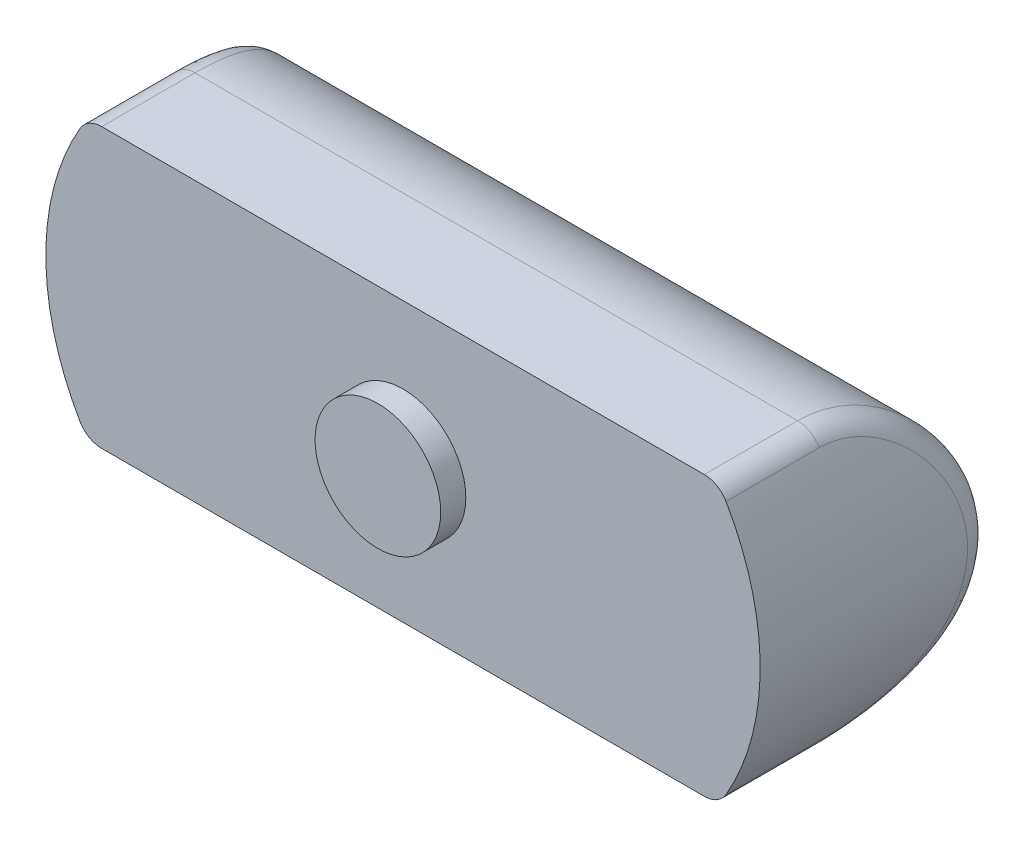
SolidWorks part; units mm, degrees
ref_plane "Front Plane" through (0, 0, 0) normal (0, 0, 1) x (1, 0, 0)
ref_plane "Top Plane" through (0, 0, 0) normal (0, 1, 0) x (1, 0, 0)
ref_plane "Right Plane" through (0, 0, 0) normal (1, 0, 0) x (0, 0, -1)
sketch "Sketch2" plane through (0, 0, 0) normal (0, 0, 1) x (1, 0, 0)
  line L0 (-37.65, 16.64) -> (37.65, 16.64)
  line L1 (42.65, 16.64) -> (42.65, -16.64) construction
  line L2 (37.65, -16.64) -> (-37.65, -16.64)
  line L3 (-42.65, -16.64) -> (-42.65, 16.64) construction
  line L4 (0, 16.64) -> (0, -16.64) construction
  arc A0 (-37.65, 16.64) -> (-37.65, -16.64) centre (-12.461, 0) ccw
  arc A1 (37.65, 16.64) -> (37.65, -16.64) centre (12.461, 0) cw
  point P2 (-34.4657, -12.2734)
  point P5 (42.65, 0)
  point P15 (0, 0)
  point P16 (0, 0)
  point P17 (-33.6669, -16.64)
  dimension "D1" = 33.28
  dimension "D2" = 85.3
  dimension "D3" = 5
  dimension "D4" = 33.28
extrude "Boss-Extrude1" add sketch "Sketch2" along normal blind 27.77
fillet "Fillet1" 2 edges at (0, 16.64, 0) (0, -16.64, 0) type full round first side face at (0, 16.64, 13.885) second side face at (0, -16.64, 13.885) middle face at (0, 0, 0)
fillet "Fillet2" radius 3 6 edges at (-37.65, 16.64, 22.205) (-37.65, -16.64, 22.205) (37.65, -16.64, 22.205) (37.65, 16.64, 22.205) (-42.65, 0, 0) (42.65, 0, 0)
sketch "Sketch3" plane through (0, 0, 27.77) normal (0, 0, 1) x (1, 0, 0)
  circle A0 centre (0, 0) radius 7.5
  dimension "D1" = 15
extrude "Boss-Extrude2" add sketch "Sketch3" along normal blind 3
sketch "Sketch4" plane through (0, -16.64, 0) normal (0, -1, 0) x (1, 0, 0)
  line L0 (-35.981, 16.64) -> (35.981, 16.64) construction
  circle A0 centre (0, 16.64) radius 6.5
  dimension "D1" = 13
extrude "Boss-Extrude3" add sketch "Sketch4" along normal blind 2 and the other way blind 3
